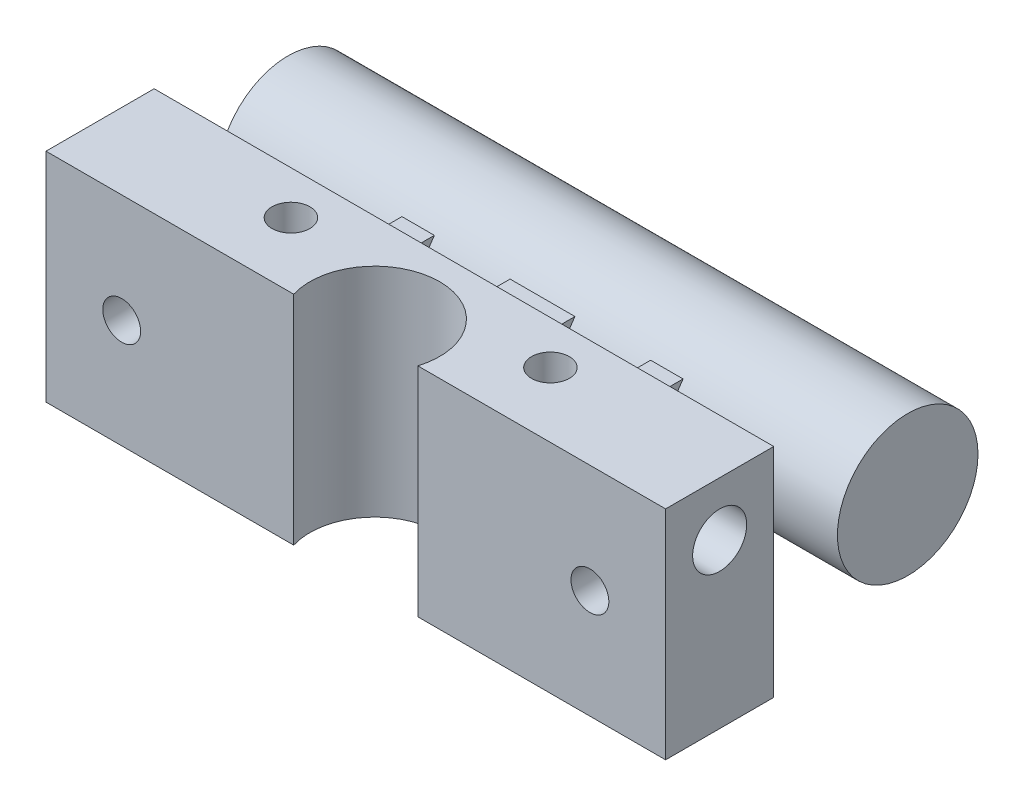
SolidWorks part; units mm, degrees
ref_plane "Front Plane" through (0, 0, 0) normal (0, 0, 1) x (1, 0, 0)
ref_plane "Top Plane" through (0, 0, 0) normal (0, 1, 0) x (1, 0, 0)
ref_plane "Right Plane" through (0, 0, 0) normal (1, 0, 0) x (0, 0, -1)
sketch "Sketch1" plane through (0, 0, 0) normal (0, 0, 1) x (1, 0, 0)
  line L0 (28.65, -10.05) -> (28.65, 10.05)
  line L1 (28.65, 10.05) -> (-28.65, 10.05)
  line L2 (-28.65, 10.05) -> (-28.65, -10.05)
  line L3 (-28.65, -10.05) -> (28.65, -10.05)
  point P5 (0, -10.05)
  point P6 (-28.65, 0)
  dimension "D1" = 57.3
  dimension "D2" = 20.1
extrude "Boss-Extrude1" add sketch "Sketch1" against normal blind 10
sketch "Sketch2" plane through (0, 0, -10) normal (0, 0, -1) x (-1, 0, 0)
  line L1 (-13, 4) -> (-10, 4)
  line L2 (-13, 4) -> (-13, -4)
  line L3 (-13, -4) -> (-10, -4)
  line L4 (-10, 4) -> (-10, -4)
  line L8 (0, 7.9704) -> (0, -7.9013) construction
  line L9 (-3, 4) -> (3, 4)
  line L10 (-3, 4) -> (-3, -4)
  line L11 (-3, -4) -> (3, -4)
  line L12 (3, 4) -> (3, -4)
  line L13 (-3, 4) -> (3, -4) construction
  line L14 (-3, -4) -> (3, 4) construction
  line L15 (13, -4) -> (10, -4)
  line L16 (10, 4) -> (10, -4)
  line L17 (13, 4) -> (10, 4)
  line L18 (13, 4) -> (13, -4)
  point P4 (-10, 0)
  point P5 (0, 0)
  dimension "D3" = 3
  dimension "D4" = 8
  dimension "D5" = 10
  dimension "D1" = 7
extrude "Boss-Extrude2" add sketch "Sketch2" along normal blind 20
sketch "Sketch3" plane through (13, 0, 0) normal (1, 0, 0) x (0, 0, -1)
  line L0 (30, 4) -> (10, 4) construction
  line L1 (30, -4) -> (10, -4) construction
  line L2 (10, -10.05) -> (10, 10.05) construction
  line L3 (22.39, 4) -> (30, 4)
  line L4 (30, 4) -> (30, -4)
  line L5 (30, -4) -> (22.39, -4)
  circle A0 centre (22.39, 0) radius 2.5
  circle A1 centre (22.39, 0) radius 1.75
  circle A2 centre (22.39, 0) radius 4
  line M5 (10, -4) -> (30, -4)
  line M6 (30, -4) -> (30, 4)
  line M7 (30, 4) -> (10, 4)
  dimension "D1" = 3.5
  dimension "D2" = 5
  dimension "D3" = 12.39
extrude "Boss-Extrude3" add sketch "Sketch3" against normal blind 4 contours A0 A1 region at (13, 0, -19.9607)
extrude "Boss-Extrude4" add sketch "Sketch3<3>" against normal blind 8 from offset 9 contours A0 A1 region at (13, 0, -19.9607) offset against normal yes
sketch "Sketch3<3>" plane through (13, 0, 0) normal (1, 0, 0) x (0, 0, -1) same geometry as "Sketch3"
mirror "Mirror1" about plane through (0, 0, 0) normal (1, 0, 0) of "Boss-Extrude3"
extrude "Cut-Extrude1" cut sketch "Sketch3<4>" against normal through all both and the other way through all contours A1 | A2 M5 M6 M7 region at (13, 0, -27.6766) region at (13, 0, -22.39)
sketch "Sketch3<4>" plane through (13, 0, 0) normal (1, 0, 0) x (0, 0, -1) same geometry as "Sketch3"
sketch "Sketch4" plane through (0, 0, -10) normal (0, 0, -1) x (-1, 0, 0)
  line L0 (-28.65, -10.05) -> (-28.65, 10.05) construction
  line L1 (28.65, 10.05) -> (28.65, -10.05) construction
  circle A0 centre (-21.65, 0) radius 1.75
  circle A1 centre (21.65, 0) radius 1.75
  dimension "D1" = 3.5
  dimension "D2" = 3.5
  dimension "D3" = 7
  dimension "D4" = 7
extrude "Cut-Extrude2" cut sketch "Sketch4" against normal through all both and the other way through all
sketch "Sketch6" plane through (0, 10.05, 0) normal (0, 1, 0) x (1, 0, 0)
  line L3 (-12, 7.75) -> (0, 7.75) construction
  line L4 (28.65, 10) -> (-28.65, 10) construction
  circle A0 centre (-12, 6) radius 1.75
  circle A1 centre (12, 6) radius 1.75
  circle A2 centre (0, 1.75) radius 6
  dimension "D1" = 3.5
  dimension "D6" = 12
  dimension "D2" = 24
  dimension "D3" = 12
  dimension "D4" = 4
extrude "Cut-Extrude3" cut sketch "Sketch6" against normal through all both and the other way through all
sketch "Sketch7" plane through (28.65, 0, 0) normal (1, 0, 0) x (0, 0, -1)
  line L0 (10, 10.05) -> (0, 10.05) construction
  circle A0 centre (5, 5.05) radius 2.5
  point P4 (5, 10.05)
  point P5 (5, 1.4936)
  dimension "D1" = 5
  dimension "D2" = 5
extrude "Cut-Extrude4" cut sketch "Sketch7" against normal blind 10
mirror "Mirror2" about plane through (0, 0, 0) normal (1, 0, 0) of "Cut-Extrude4"
sketch "Sketch5" plane through (13, 0, 0) normal (1, 0, 0) x (0, 0, -1)
  circle A0 centre (22.39, 0) radius 6.5
  dimension "D1" = 13
extrude "Boss-Extrude6" add sketch "Sketch5" along normal through all and the other way through all
